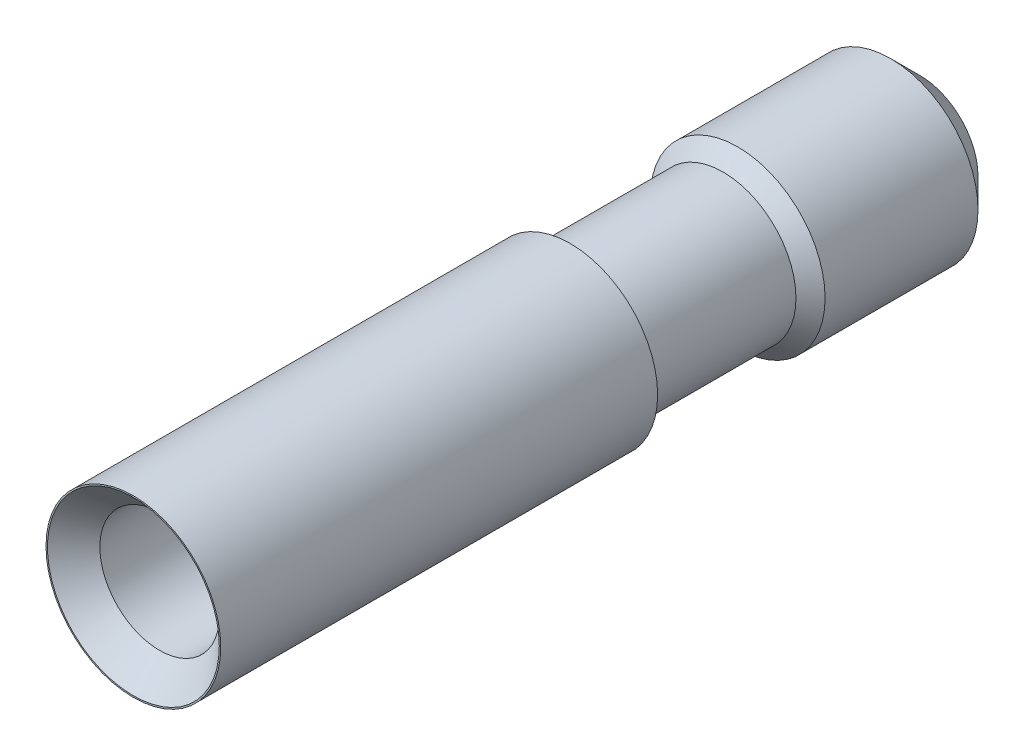
SolidWorks part; units mm, degrees
material "1.4000 (X6Cr13)"
ref_plane "Plan de face" through (0, 0, 0) normal (0, 0, 1) x (1, 0, 0)
ref_plane "Plan de dessus" through (0, 0, 0) normal (0, 1, 0) x (1, 0, 0)
ref_plane "Plan de droite" through (0, 0, 0) normal (1, 0, 0) x (0, 0, -1)
sketch "Esquisse1" plane through (0, 0, 0) normal (0, 0, 1) x (1, 0, 0)
  circle A0 centre (0, 0) radius 3
  dimension "D1" = 6
extrude "Boss.-Extru.1" add sketch "Esquisse1" along normal blind 27 contours A0
cosmetic thread "Représentation de filetage1" parameters "D1"=5, "D2"=4.891
sketch "Esquisse7" plane through (0, 0, 27) normal (0, 0, 1) x (1, 0, 0)
  circle A1 centre (0, 0) radius 2.05
  dimension "D1" = 4.1
hole_wizard "Diamètre du perçage Ø2.5 (2.5)2" positions "Esquisse5" profile "Esquisse4" hole size "Ø2.5" standard "ISO"
sketch "Esquisse5" plane through (0, 0, 0) normal (0, 0, -1) x (-1, 0, 0)
  point P0 (0, 0)
sketch "Esquisse4" plane through (0, 0, 0) normal (1, 0, 0) x (0, 1, 0)
  line L0 (0, 0) -> (0, 3)
  line L1 (0, 3) -> (1.25, 3)
  line L2 (1.25, 3) -> (1.25, 0)
  line L5 (1.25, 0) -> (0, 0)
  line L10 (0, 3) -> (-1.25, 3) construction
  line L11 (0, -6.35) -> (0, 107.95) construction
  dimension "Diamètre du perçage" = 2.5
  dimension "Profondeur du perçage" = 3
  dimension "Angle de pointe" = 180
sketch "Esquisse6" plane through (0, 0, 27) normal (0, 0, 1) x (1, 0, 0)
  line L1 (-6.0949, -5.2635) -> (5.6553, -5.2635)
  line L2 (-6.0949, -5.2635) -> (-6.0949, 6.1211)
  line L3 (-6.0949, 6.1211) -> (5.6553, 6.1211)
  line L4 (5.6553, -5.2635) -> (5.6553, 6.1211)
  circle A0 centre (0, 0) radius 2.5
  dimension "D1" = 5
extrude "Enlèv. mat.-Extru.1" cut sketch "Esquisse6" against normal blind 6 from offset 15 offset against normal yes
chamfer "Chanfrein1" distance 1 angle 45 1 edges at (3, 0, 0)
chamfer "Chanfrein2" distance 0.75 angle 45 1 edges at (2.5, 0, 6)
extrude "Enlèv. mat.-Extru.2" cut sketch "Esquisse7" against normal blind 24.5
chamfer "Chanfrein4" distance 0.9 angle 45 1 edges at (2.05, 0, 27)
